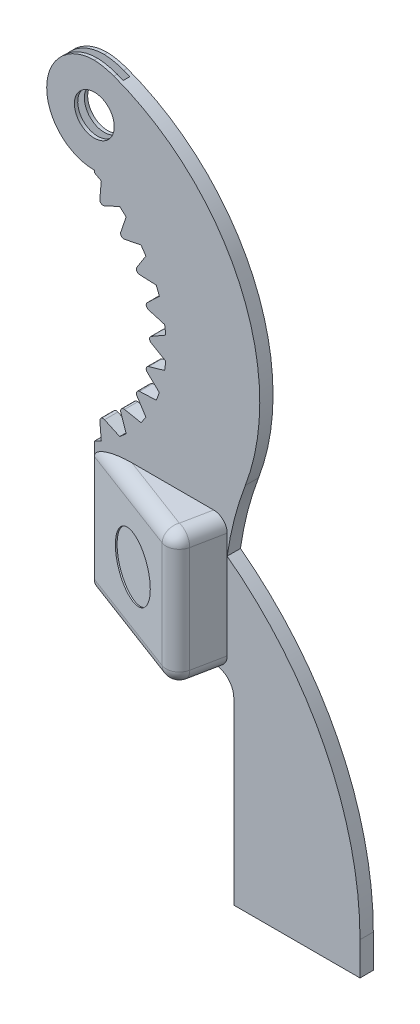
SolidWorks part; units mm, degrees
ref_plane "Front Plane" through (0, 0, 0) normal (0, 0, 1) x (1, 0, 0)
ref_plane "Top Plane" through (0, 0, 0) normal (0, 1, 0) x (1, 0, 0)
ref_plane "Right Plane" through (0, 0, 0) normal (1, 0, 0) x (0, 0, -1)
sketch "Sketch1" plane through (0, 0, 0) normal (0, 0, 1) x (1, 0, 0)
  line L0 (0, 50) -> (0, -50) construction
  line L1 (-20, 50) -> (20, 50) construction
  line L2 (-20, 50) -> (-20, -50) construction
  line L3 (-20, -50) -> (20, -50) construction
  line L4 (20, 50) -> (20, -50) construction
  line L5 (-20, 50) -> (20, -50) construction
  line L6 (-20, -50) -> (20, 50) construction
  line L7 (-20, -20) -> (20, -20) construction
  line L8 (-20, -5) -> (20, -5) construction
  line L9 (-20, -5) -> (-20, -20)
  line L10 (-20, -20) -> (0, -20)
  line L11 (20, -50) -> (1, -50)
  line L12 (1, -50) -> (1, -20)
  line L13 (20, -50) -> (20, -5)
  line L14 (20, -5) -> (0, -5)
  line L15 (-20, 0) -> (0, 0) construction
  line L16 (-20, -5) -> (-20, 0)
  line L17 (0, -5) -> (0, 0)
  line L18 (-20, 50) -> (-20, 35)
  line L19 (1, -20) -> (0, -20)
  arc A0 (-20, 50) -> (0, 0) centre (-28.75, 17.5) cw
  arc A1 (-20, 35) -> (-20, 0) centre (-28.75, 17.5) cw
  point P0 (0, 0)
  point P8 (1, -50)
  point P18 (-20, 35)
  dimension "D1" = 40
  dimension "D2" = 100
  dimension "D4" = 30
  dimension "D5" = 15
  dimension "D6" = 5
  dimension "D7" = 15
  dimension "D8" = 19
extrude "Boss-Extrude1" add sketch "Sketch1" along normal blind 2
sketch "Sketch2" plane through (0, 0, 2) normal (0, 0, 1) x (1, 0, 0)
  line L0 (-20, 35) -> (-20, 0) construction
  line L1 (-20, 17.5) -> (-9.1844, 17.5) construction
  line L3 (-12.1844, 17.5) -> (-8.5113, 19.6207)
  line L4 (-12.1844, 17.5) -> (-8.5113, 15.3793)
  line L5 (-8.5113, 19.6207) -> (-8.5113, 15.3793)
  arc A0 (-20, 0) -> (-20, 35) centre (-28.75, 17.5) ccw construction
extrude "Boss-Extrude2" add sketch "Sketch2" against normal up to vertex (2 mm away) up to point (-20, 35, 0)
pattern_circular "CirPattern1" count 5 over 55 about axis through (-28.75, 17.5, 2) along (0, 0, -1) of "Boss-Extrude2"
pattern_circular "CirPattern2" count 5 every 13.75 about axis through (-28.75, 17.5, 2) along (0, 0, -1) of "CirPattern1" reverse direction yes
ref_plane "Plane1" through (0, 0, 0) normal (0, 1, 0) x (-1, 0, 0)
sketch "Sketch6" plane through (0, 0, 0) normal (0, 1, 0) x (-1, 0, 0)
  line L0 (1.4057, 9) -> (1.4057, 2) construction
  line L1 (20, 2) -> (-5.5943, 2) construction
  line L2 (20, 2) -> (20, 9) construction
  line L3 (20, 9) -> (-5.5943, 9) construction
  line L4 (-5.5943, 2) -> (-5.5943, 9) construction
  line L5 (20, 2) -> (1.4057, 9)
  line L6 (1.4057, 9) -> (0, 2)
  line L7 (0, 2) -> (20, 2)
  point P6 (20, 2)
extrude "Boss-Extrude3" add sketch "Sketch6" against normal up to vertex (20 mm away) up to point (-20, -20, 2)
sketch "Sketch7" plane through (-3.142, 0, 8.3463) normal (-0.3523, 0, 0.9359) x (0.9359, 0, 0.3523)
  line L0 (-18.0129, -10) -> (1.8553, -10) construction
  line L1 (-18.0129, 0) -> (-18.0129, -20) construction
  line L2 (1.8553, -20) -> (1.8553, 0) construction
  line L3 (-8.0788, -20) -> (-8.0788, 0) construction
  line L4 (-18.0129, -20) -> (1.8553, -20) construction
  circle A0 centre (-8.0788, -10) radius 4.5
  dimension "D1" = 9
extrude "Cut-Extrude1" cut sketch "Sketch7" against normal blind 0.2
fillet "Fillet1" radius 2 5 edges at (-0.7028, 0, 5.5) (-0.7028, -20, 5.5) (-10.7028, 0, 5.5) (-10.7028, -20, 5.5) (-1.4057, -10, 9)
ref_plane "Plane2" through (0, 0, 2) normal (0, 0, 1) x (1, 0, 0)
sketch "Sketch15" plane through (0, 0, 2) normal (0, 0, 1) x (1, 0, 0)
  line L0 (-20, 50) -> (-20, 35) construction
  circle A0 centre (-20, 42.5) radius 7.1703
extrude "Boss-Extrude6" add sketch "Sketch15" against normal up to vertex (2 mm away) up to point (-20, 50, 0)
sketch "Sketch16" plane through (0, 0, 2) normal (0, 0, 1) x (1, 0, 0)
  circle A0 centre (-20, 42.5) radius 3
  dimension "D1" = 6
extrude "Cut-Extrude2" cut sketch "Sketch16" against normal through all
ref_plane "Plane3" through (-30, 0, 0) normal (1, 0, 0) x (0, 0, -1)
sketch "Sketch17" plane through (-30, 0, 0) normal (1, 0, 0) x (0, 0, -1)
  line L0 (-1, 49.6703) -> (-1, 35.3297) construction
  line L1 (0, 49.6703) -> (-2, 49.6703) construction
  line L2 (-2, 35.3297) -> (0, 35.3297) construction
  line L4 (-0.5, 47.5) -> (-1.5, 47.5)
  line L5 (-0.5, 47.5) -> (-0.5, 37.5)
  line L6 (-0.5, 37.5) -> (-1.5, 37.5)
  line L7 (-1.5, 47.5) -> (-1.5, 37.5)
  line L8 (-0.5, 47.5) -> (-1.5, 37.5) construction
  line L9 (-0.5, 37.5) -> (-1.5, 47.5) construction
  point P6 (-1, 42.5)
  dimension "D1" = 1
  dimension "D2" = 10
extrude "Cut-Extrude3" cut sketch "Sketch17" along normal blind 14
ref_plane "Plane4" through (0, 55, 0) normal (0, 1, 0) x (-1, 0, 0)
sketch "Sketch18" plane through (0, 55, 0) normal (0, 1, 0) x (-1, 0, 0)
  line L1 (25.1393, 0.5) -> (16.1393, 0.5)
  line L2 (25.1393, 0.5) -> (25.1393, 1.5)
  line L3 (25.1393, 1.5) -> (16.1393, 1.5)
  line L4 (16.1393, 0.5) -> (16.1393, 1.5)
  dimension "D1" = 1
  dimension "D2" = 9
extrude "Cut-Extrude4" cut sketch "Sketch18" against normal blind 20
fillet "Fillet2" radius 10 2 edges at (-20, 50, 0.25) (-20, 50, 1.75)
fillet "Fillet3" radius 50 2 edges at (20, -5, 1) (0, 0, 1)
fillet "Fillet5" radius 0.5 9 edges at (-19.2484, 3.9303, 1) (-16.2953, 6.5775, 1) (-14.0561, 9.8509, 1) (-12.6591, 13.5626, 1) (-12.1844, 17.5, 1) (-12.6591, 21.4374, 1) (-14.0561, 25.1491, 1) (-16.2953, 28.4225, 1) (-19.2484, 31.0697, 1)
fillet "Fillet6" radius 3 1 edges at (1, -20, 1)
